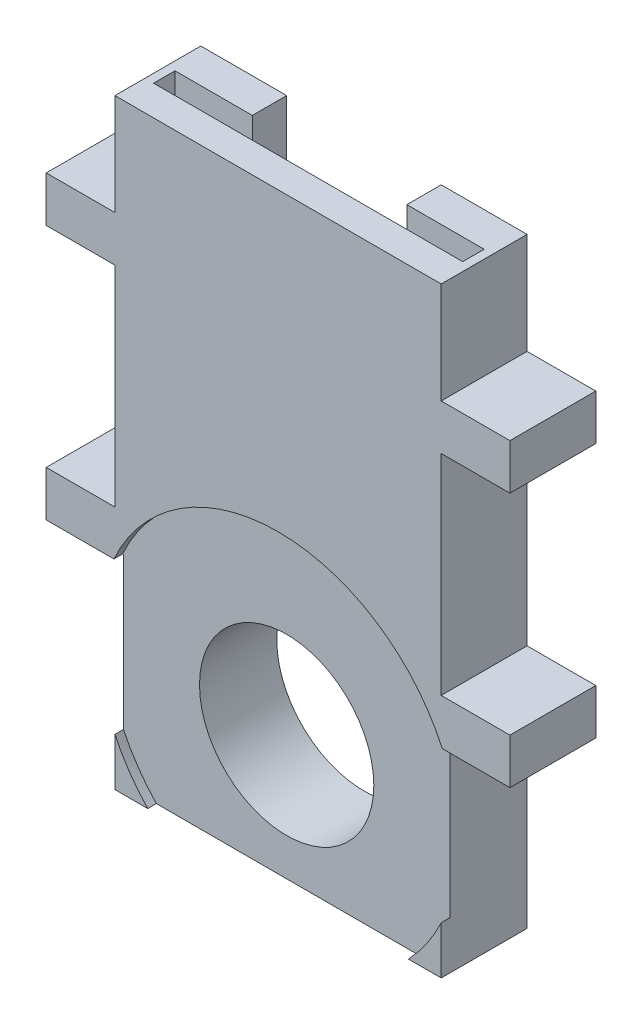
SolidWorks part; units mm, degrees
ref_plane "Front Plane" through (0, 0, 0) normal (0, 0, 1) x (1, 0, 0)
ref_plane "Top Plane" through (0, 0, 0) normal (0, 1, 0) x (1, 0, 0)
ref_plane "Right Plane" through (0, 0, 0) normal (1, 0, 0) x (0, 0, -1)
sketch "Sketch2" plane through (0, 0, 0) normal (0, 0, 1) x (1, 0, 0)
  line L1 (-16.8293, 25.5691) -> (2.1707, 25.5691)
  line L2 (-16.8293, 25.5691) -> (-16.8293, -9.4309)
  line L3 (-16.8293, -9.4309) -> (2.1707, -9.4309)
  line L4 (2.1707, 25.5691) -> (2.1707, -9.4309)
  dimension "D1" = 35
  dimension "D2" = 19
extrude "Boss-Extrude1" add sketch "Sketch2" along normal blind 5
ref_plane "Plane1" through (-7.3293, 0, 0) normal (1, 0, 0) x (0, 0, -1)
sketch "Sketch3" plane through (-7.3293, 0, 0) normal (1, 0, 0) x (0, 0, -1)
  line L0 (-5, -9.4309) -> (-5, 25.5691) construction
  line L1 (-5, 19.6691) -> (0, 19.6691)
  line L2 (-5, 19.6691) -> (-5, 17.0191)
  line L3 (-5, 17.0191) -> (0, 17.0191)
  line L4 (0, 19.6691) -> (0, 17.0191)
  line L5 (0, -9.4309) -> (0, 25.5691) construction
  line L6 (-5, 25.5691) -> (0, 25.5691) construction
  line L7 (-5, 4.8191) -> (0, 4.8191)
  line L8 (-5, 4.8191) -> (-5, 2.1691)
  line L9 (-5, 2.1691) -> (0, 2.1691)
  line L10 (0, 4.8191) -> (0, 2.1691)
  dimension "D1" = 2.65
  dimension "D2" = 2.65
  dimension "D3" = 12.2
  dimension "D4" = 5.9
extrude "Boss-Extrude2" add sketch "Sketch3" along normal blind 13.5
extrude "Boss-Extrude3" add sketch "Sketch3<2>" against normal blind 13.5
sketch "Sketch3<2>" plane through (-7.3293, 0, 0) normal (1, 0, 0) x (0, 0, -1) same geometry as "Sketch3"
sketch "Sketch4" plane through (0, 0, 5) normal (0, 0, 1) x (1, 0, 0)
  line L0 (-16.8293, 25.5691) -> (2.1707, 25.5691) construction
  line L1 (-7.3293, 25.5691) -> (-7.3293, -9.4309) construction
  line L2 (-16.8293, -9.4309) -> (2.1707, -9.4309) construction
  circle A0 centre (-7.3293, -2.1737) radius 5.075
extrude "Cut-Extrude1" cut sketch "Sketch4" against normal through all
sketch "Sketch5" plane through (0, 0, 5) normal (0, 0, 1) x (1, 0, 0)
  circle A0 centre (-7.3293, -2.1737) radius 10.5
  dimension "D1" = 21
extrude "Cut-Extrude2" cut sketch "Sketch5" against normal blind 0.5
ref_plane "Plane2" through (-5.7786, 7.3761, 2.025) normal (-0.4018, 0.9157, 0) x (0, 0, -1)
sketch "Sketch7" plane through (0, 25.5691, 0) normal (0, 1, 0) x (1, 0, 0)
  line L0 (-16.8293, -5) -> (-16.8293, 0) construction
  line L1 (-16.3293, -3.25) -> (1.6707, -3.25)
  line L2 (-16.3293, -3.25) -> (-16.3293, -2)
  line L3 (-16.3293, -2) -> (1.6707, -2)
  line L4 (1.6707, -3.25) -> (1.6707, -2)
  line L6 (2.1707, 0) -> (-16.8293, 0) construction
  dimension "D3" = 0.5
  dimension "D1" = 18
  dimension "D2" = 1.25
  dimension "D4" = 2
extrude "Cut-Extrude3" cut sketch "Sketch7" against normal blind 22.2
sketch "Sketch8" plane through (0, 25.5691, 0) normal (0, 1, 0) x (1, 0, 0)
  line L0 (1.6707, -2) -> (-16.3293, -2) construction
  line L1 (-11.8293, -2) -> (-2.8293, -2)
  line L2 (-11.8293, -2) -> (-11.8293, 0)
  line L3 (-11.8293, 0) -> (-2.8293, 0)
  line L4 (-2.8293, -2) -> (-2.8293, 0)
  line L5 (2.1707, 0) -> (-16.8293, 0) construction
  line L6 (2.1707, -5) -> (2.1707, 0) construction
  dimension "D1" = 9
  dimension "D2" = 5
extrude "Cut-Extrude4" cut sketch "Sketch8" against normal blind 19
sketch "Sketch9" plane through (0, 2.1691, 0) normal (0, -1, 0) x (1, 0, 0)
  line L0 (-20.8293, 0) -> (-16.8293, 0) construction
  line L1 (-20.5293, 4.5) -> (-17.1293, 4.5)
  line L2 (-20.5293, 4.5) -> (-20.5293, 3.5)
  line L4 (-17.1293, 4.5) -> (-17.1293, 3.5)
  line L14 (-20.5293, 1.5) -> (-20.5293, 0.5)
  line L15 (-20.5293, 0.5) -> (-17.1293, 0.5)
  line L16 (-17.1293, 1.5) -> (-17.1293, 0.5)
  line L17 (-20.8293, 5) -> (-16.8891, 5) construction
  line L18 (-20.8293, 5) -> (-20.8293, 0) construction
  line L19 (-16.8293, 4.5) -> (-16.8293, 0) construction
  line L20 (2.4707, 4.5) -> (5.8707, 4.5)
  line L21 (2.4707, 4.5) -> (2.4707, 3.5)
  line L23 (5.8707, 4.5) -> (5.8707, 3.5)
  line L24 (2.4707, 3.5) -> (2.4707, 1.5)
  line L25 (5.8707, 3.5) -> (5.8707, 1.5)
  line L30 (2.4707, 1.5) -> (2.4707, 0.5)
  line L31 (2.4707, 0.5) -> (5.8707, 0.5)
  line L32 (5.8707, 1.5) -> (5.8707, 0.5)
  line L33 (6.1707, 5) -> (6.1707, 0) construction
  line L34 (2.1707, 4.5) -> (2.1707, 0) construction
  line L35 (6.1707, 5) -> (2.2305, 5) construction
  line L36 (6.1707, 0) -> (2.1707, 0) construction
  line L37 (-20.5293, 3.5) -> (-20.5293, 1.5)
  line L38 (-17.1293, 3.5) -> (-17.1293, 1.5)
  dimension "D1" = 0.5
  dimension "D2" = 0.5
  dimension "D7" = 0.3
  dimension "D8" = 0.3
  dimension "D11" = 1
  dimension "D12" = 1
  dimension "D13" = 0.3
  dimension "D14" = 0.3
  dimension "D15" = 0.5
  dimension "D16" = 0.5
extrude "Cut-Extrude5" cut sketch "Sketch9" against normal blind 1 contours L4 L1 L2 | L16 L14 L15 | L32 L30 L31 | L23 L25 L32 L31 L30 L24 L21 L20 region at (-18.8293, 2.1691, 2.5) region at (4.1707, 2.1691, 2.5)
sketch "Sketch10" plane through (0, 17.0191, 0) normal (0, -1, 0) x (1, 0, 0)
  line L1 (-20.5293, 4.5) -> (-17.1293, 4.5)
  line L2 (-20.5293, 4.5) -> (-20.5293, 0.5)
  line L3 (-20.5293, 0.5) -> (-17.1293, 0.5)
  line L4 (-17.1293, 4.5) -> (-17.1293, 0.5)
  line L5 (2.4707, 4.5) -> (5.8707, 4.5)
  line L6 (2.4707, 4.5) -> (2.4707, 0.5)
  line L7 (2.4707, 0.5) -> (5.8707, 0.5)
  line L8 (5.8707, 4.5) -> (5.8707, 0.5)
extrude "Cut-Extrude6" cut sketch "Sketch10" against normal blind 1
